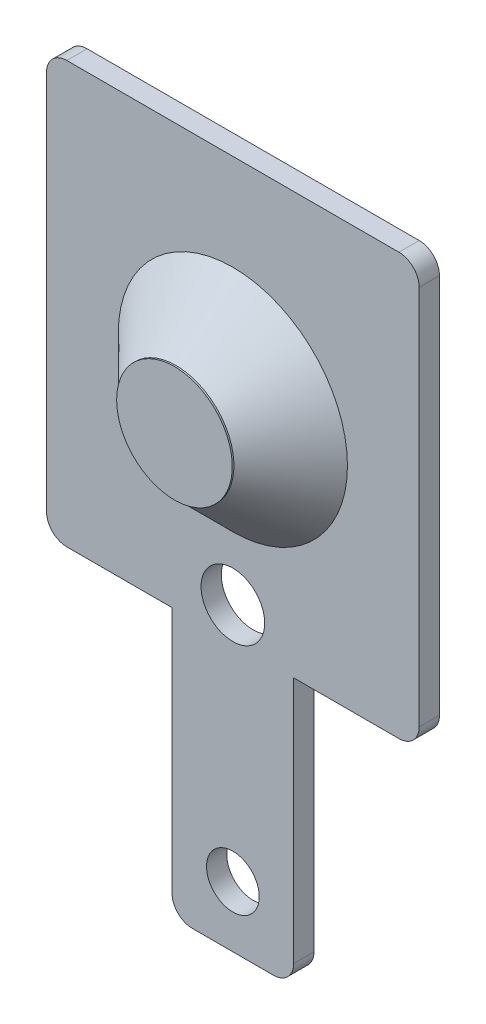
SolidWorks part; units mm, degrees
ref_plane "Front" through (0, 0, 0) normal (0, 0, 1) x (1, 0, 0)
ref_plane "Top" through (0, 0, 0) normal (0, 1, 0) x (1, 0, 0)
ref_plane "Right" through (0, 0, 0) normal (1, 0, 0) x (0, 0, -1)
sketch "Sketch1" plane through (0, 0, 0) normal (0, 0, 1) x (1, 0, 0)
  line L0 (0, 0) -> (9.19, 0)
  line L1 (9.19, 0) -> (9.19, -10.3886)
  line L3 (3.095, -10.3886) -> (3.095, -16.99)
  line L4 (3.095, -16.99) -> (6.095, -16.99)
  line L5 (6.095, -16.99) -> (6.095, -10.3886)
  line L7 (0, -10.3886) -> (0, 0)
  line L8 (4.595, -16.99) -> (4.595, -15.49) construction
  line L9 (0, -10.3886) -> (3.095, -10.3886)
  line L10 (6.095, -10.3886) -> (9.19, -10.3886)
  circle A0 centre (4.595, -15.49) radius 0.65
  circle A1 centre (4.595, -9.5786) radius 0.785
  dimension "D6" = 1.3
  dimension "D7" = 1.57
  dimension "D1" = 10.3886
  dimension "D2" = 9.19
  dimension "D3" = 3
  dimension "D4" = 16.99
  dimension "D5" = 1.5
  dimension "D8" = 0.81
extrude "Boss-Extrude1" add sketch "Sketch1" along normal blind 0.5
sketch "Sketch2" plane through (0, 0, 0.5) normal (0, 0, 1) x (1, 0, 0)
  circle A0 centre (4.595, -9.5786) radius 1.245
  circle A1 centre (4.595, -9.5786) radius 0.785
  dimension "D1" = 2.49
extrude "Boss-Extrude2" [suppressed] add sketch "Sketch2" along normal blind 0.35
fillet "Fillet1" radius 0.5 6 edges at (9.19, -10.3886, 0.25) (0, 0, 0.25) (9.19, 0, 0.25) (6.095, -16.99, 0.25) (3.095, -16.99, 0.25) (0, -10.3886, 0.25)
sketch "Sketch4" plane through (0, 0, 0.5) normal (0, 0, 1) x (1, 0, 0)
  line L0 (0, -5.1943) -> (9.19, -5.1943) construction
  line L1 (0, -0.5) -> (0, -9.8886) construction
  line L2 (9.19, -9.8886) -> (9.19, -0.5) construction
  circle A0 centre (4.595, -5.1943) radius 2.5677
  point P8 (0, 0)
curve "Helix/Spiral1"
ref_plane "Plane2" through (0, -5.1943, 0) normal (0, -1, 0) x (-1, 0, 0)
sketch "Sketch5" plane through (0, -5.1943, 0) normal (0, -1, 0) x (-1, 0, 0)
  circle A0 centre (-2.0273, -0.5) radius 0.2653
  point P2 (0, 0)
sweep "Sweep1" [suppressed] add profiles "Sketch5" path "Helix/Spiral1"
sketch "Sketch6" plane through (0, 0, 0.5) normal (0, 0, 1) x (1, 0, 0)
  line L0 (0, -5.1943) -> (9.19, -5.1943) construction
  line L1 (0, -0.5) -> (0, -9.8886) construction
  line L2 (9.19, -9.8886) -> (9.19, -0.5) construction
  circle A0 centre (4.595, -5.1943) radius 1.4262
extrude "Boss-Extrude3" add sketch "Sketch6" along normal blind 1.44
chamfer "Chamfer1" distance 1.4 angle 45 1 edges at (3.1688, -5.1943, 0.5)
ref_plane "Plane3" through (4.595, 0, 0) normal (-1, 0, 0) x (0, 0, 1)
ref_axis "Axis1" through (4.595, -10.3886, -0.025) along (0, 0, 1)
ref_plane "Plane4" through (0, 0, 0.25) normal (0, 0, 1) x (1, 0, 0)
ref_point "Point1"
